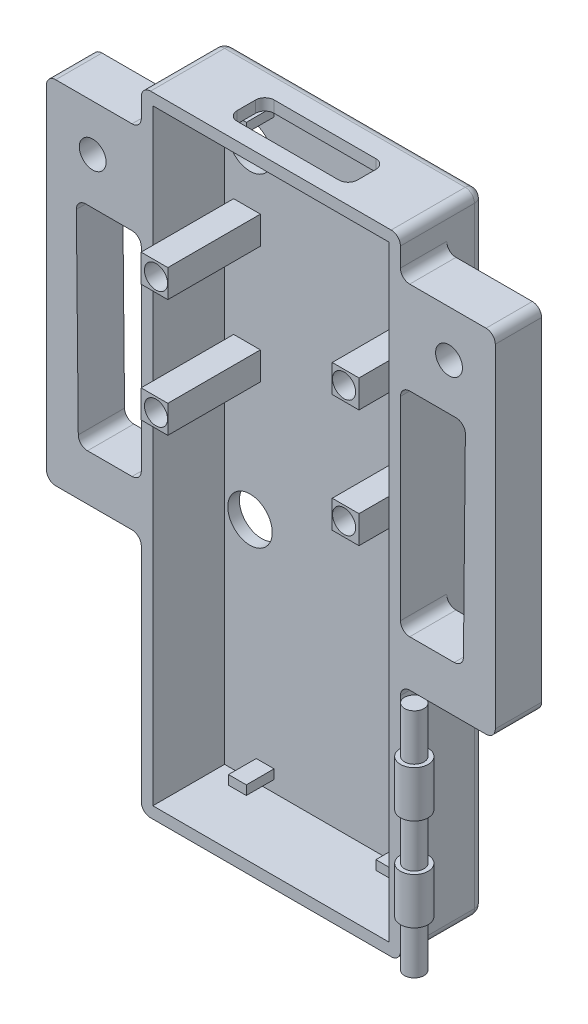
SolidWorks part; units mm, degrees
ref_plane "Front Plane" through (0, 0, 0) normal (0, 0, 1) x (1, 0, 0)
ref_plane "Top Plane" through (0, 0, 0) normal (0, 1, 0) x (1, 0, 0)
ref_plane "Right Plane" through (0, 0, 0) normal (1, 0, 0) x (0, 0, -1)
sketch "Sketch1" plane through (0, 0, 0) normal (0, 0, 1) x (1, 0, 0)
  line L0 (-14, 34) -> (14, -34) construction
  line L1 (-14, 34) -> (14, 34)
  line L2 (-14, 34) -> (-14, -34)
  line L3 (-14, -34) -> (14, -34)
  line L4 (14, 34) -> (14, -34)
  point P4 (0, 0)
  dimension "D1" = 68
  dimension "D2" = 28
extrude "Boss-Extrude1" add sketch "Sketch1" along normal blind 1.25
sketch "Sketch21" plane through (0, 0, 1.25) normal (0, 0, 1) x (1, 0, 0)
  line L0 (-14, 34) -> (-14, 31.5) construction
  line L1 (-14, 34) -> (-14, -34) construction
  line L2 (-9.3284, 30.5) -> (-9.3284, -30.4933) construction
  line L3 (-14, 0.0033) -> (14, 0.0033) construction
  line L4 (14, -34) -> (14, 34) construction
  line L5 (-0.4034, 30.5) -> (6.5966, 30.5) construction
  line L6 (-0.4034, 30.5) -> (-7.4034, 30.5) construction
  line L7 (-7.4034, 30.5) -> (-9.3284, 30.5)
  line L8 (-7.4034, 30.5) -> (-7.4034, 31.5)
  line L9 (-7.4034, 31.5) -> (-9.3284, 31.5)
  line L10 (-9.3284, 30.5) -> (-9.3284, 31.5)
  line L11 (6.5966, 30.5) -> (8.5216, 30.5)
  line L12 (6.5966, 30.5) -> (6.5966, 31.5)
  line L13 (6.5966, 31.5) -> (8.5216, 31.5)
  line L14 (8.5216, 30.5) -> (8.5216, 31.5)
  line L15 (6.5966, -31.4933) -> (8.5216, -31.4933)
  line L16 (8.5216, -30.4933) -> (8.5216, -31.4933)
  line L17 (6.5966, -30.4933) -> (8.5216, -30.4933)
  line L18 (6.5966, -30.4933) -> (6.5966, -31.4933)
  line L19 (-7.4034, -31.4933) -> (-9.3284, -31.4933)
  line L20 (-9.3284, -30.4933) -> (-9.3284, -31.4933)
  line L21 (-7.4034, -30.4933) -> (-9.3284, -30.4933)
  line L22 (-7.4034, -30.4933) -> (-7.4034, -31.4933)
  line L23 (-14, -34) -> (14, -34) construction
  line L24 (8.5216, 30.5) -> (8.5216, -30.4933) construction
  line L25 (7.5591, 31.5) -> (7.5591, 34) construction
  line L26 (14, 34) -> (-14, 34) construction
  line L27 (-7.4034, -31.4933) -> (6.5966, -31.4933) construction
  line L28 (-7.4034, 30.5) -> (-7.4034, 0.0033) construction
  dimension "D1" = 1.925
  dimension "D2" = 1
  dimension "D3" = 1.925
  dimension "D4" = 1
  dimension "D5" = 60.9933
  dimension "D6" = 60.9933
extrude "Boss-Extrude10" add sketch "Sketch21" along normal blind 3
sketch "Sketch22" plane through (0, 0, 1.25) normal (0, 0, 1) x (1, 0, 0)
  line L0 (-11.7716, 7.9708) -> (-14, 7.9708) construction
  line L1 (0, 34) -> (0, 0) construction
  line L2 (8.8816, 20.6708) -> (11.7716, 20.6708)
  line L3 (8.8816, 20.6708) -> (8.8816, 17.6708)
  line L4 (8.8816, 17.6708) -> (11.7716, 17.6708)
  line L5 (11.7716, 20.6708) -> (11.7716, 17.6708)
  line L6 (14, 34) -> (-14, 34) construction
  line L7 (-10.16, 6.4708) -> (10.16, 6.4708) construction
  line L8 (-8.8816, 17.6708) -> (-11.7716, 17.6708)
  line L9 (-11.7716, 20.6708) -> (-11.7716, 17.6708)
  line L10 (-8.8816, 20.6708) -> (-11.7716, 20.6708)
  line L11 (-8.8816, 20.6708) -> (-8.8816, 17.6708)
  line L12 (11.7716, 7.9708) -> (14, 7.9708) construction
  line L15 (11.7716, 4.9708) -> (14, 4.9708) construction
  line L16 (8.8816, 7.9708) -> (11.7716, 7.9708)
  line L17 (11.7716, 4.9708) -> (11.7716, 7.9708)
  line L18 (8.8816, 4.9708) -> (11.7716, 4.9708)
  line L19 (8.8816, 4.9708) -> (8.8816, 7.9708)
  line L20 (-8.8816, 4.9708) -> (-8.8816, 7.9708)
  line L21 (-8.8816, 4.9708) -> (-11.7716, 4.9708)
  line L22 (-11.7716, 4.9708) -> (-11.7716, 7.9708)
  line L23 (-8.8816, 7.9708) -> (-11.7716, 7.9708)
  line L24 (14, -34) -> (14, 34) construction
  line L25 (-11.7716, 4.9708) -> (-14, 4.9708) construction
  line L26 (-14, 34) -> (-14, -34) construction
  circle A0 centre (10.16, 19.1708) radius 1.25
  circle A1 centre (-10.16, 19.1708) radius 1.25
  circle A2 centre (10.16, 6.4708) radius 1.25
  circle A3 centre (-10.16, 6.4708) radius 1.25
  dimension "D3" = 2.5
  dimension "D1" = 3
  dimension "D2" = 2.89
  dimension "D7" = 3
extrude "Boss-Extrude11" add sketch "Sketch22" along normal blind 10
sketch "Sketch7" plane through (0, 0, 1.25) normal (0, 0, 1) x (1, 0, 0)
  line L0 (14, -34) -> (14, 34) construction
  line L1 (-12.75, 32.75) -> (12.75, 32.75)
  line L2 (-12.75, 32.75) -> (-12.75, -32.75)
  line L3 (-12.75, -32.75) -> (12.75, -32.75)
  line L4 (12.75, 32.75) -> (12.75, -32.75)
  line L5 (14, 34) -> (-14, 34) construction
  line L6 (-14, 34) -> (-14, -34) construction
  line L7 (-14, -34) -> (14, -34) construction
  line L9 (-14, 34) -> (14, 34)
  line L10 (-14, 34) -> (-14, -34)
  line L11 (-14, -34) -> (14, -34)
  line L12 (14, 34) -> (14, -34)
  dimension "D1" = 1.25
  dimension "D2" = 1.25
  dimension "D3" = 1.25
  dimension "D4" = 1.25
extrude "Boss-Extrude4" add sketch "Sketch7" along normal blind 7.75
sketch "Sketch18" plane through (0, 34, 0) normal (0, 1, 0) x (1, 0, 0)
  line L0 (0, 0) -> (0, -5.15) construction
  line L1 (14, 0) -> (-14, 0) construction
  line L3 (-6.5, -3.15) -> (6.5, -3.15)
  line L4 (-6.5, -3.15) -> (-6.5, -7.15)
  line L5 (-6.5, -7.15) -> (6.5, -7.15)
  line L6 (6.5, -3.15) -> (6.5, -7.15)
  line L7 (-6.5, -3.15) -> (6.5, -7.15) construction
  line L8 (-6.5, -7.15) -> (6.5, -3.15) construction
  dimension "D1" = 13
  dimension "D2" = 4
  dimension "D3" = 3.15
extrude "Cut-Extrude10" cut sketch "Sketch18" against normal up to surface (1.25 mm away) up to face at (0, 32.75, 5.125)
sketch "Sketch17" plane through (0, 0, 1.25) normal (0, 0, 1) x (1, 0, 0)
  line L0 (14, 34) -> (-14, 34) construction
  line L1 (5.5, 35.25) -> (-5.5, 35.25)
  line L2 (5.5, 35.25) -> (5.5, 32.75)
  line L3 (5.5, 32.75) -> (-5.5, 32.75)
  line L4 (-5.5, 35.25) -> (-5.5, 32.75)
  line L5 (5.5, 35.25) -> (-5.5, 32.75) construction
  line L6 (5.5, 32.75) -> (-5.5, 35.25) construction
  line L7 (12.75, 32.75) -> (-12.75, 32.75) construction
  point P0 (0, 34)
  dimension "D1" = 11
sketch "Sketch13" plane through (0, -34, 0) normal (0, -1, 0) x (1, 0, 0)
  line L0 (14, 9) -> (15.5, 9) construction
  line L1 (15.5, 7.5) -> (14, 6.3032)
  line L2 (14, 9) -> (14, 0) construction
  line L3 (14, 9) -> (14, 6.3032)
  line L4 (-14, 0) -> (14, 0) construction
  arc A0 (15.5, 7.5) -> (14, 9) centre (15.5, 9) ccw
  circle A1 centre (15.5, 9) radius 1.05
  dimension "D1" = 2.1
  dimension "D2" = 1.5
  dimension "D3" = 6.3032
extrude "Boss-Extrude7" add sketch "Sketch13" against normal blind 5
pattern_linear "LPattern2" count 4 spacing 5 along (0, 1, 0) skipping (2, 0) of "Boss-Extrude7"
sketch "Sketch14" plane through (14, 0, 0) normal (1, 0, 0) x (0, 0, -1)
  line L1 (-11.8523, -34) -> (-1.8523, -34)
  line L2 (-11.8523, -34) -> (-11.8523, -29)
  line L3 (-11.8523, -29) -> (-1.8523, -29)
  line L4 (-1.8523, -34) -> (-1.8523, -29)
  line L6 (-6.3032, -34) -> (0, -34) construction
  dimension "D1" = 5
  dimension "D2" = 10
extrude "Cut-Extrude5" cut sketch "Sketch14" along normal blind 5
sketch "Sketch5" [suppressed] plane through (0, 0, 1.25) normal (0, 0, 1) x (1, 0, 0)
  line L0 (-2.3257, 30.0894) -> (-2.3257, -35.4106) construction
  line L1 (9.9243, 30.0894) -> (-14.5757, 30.0894) construction
  line L2 (-14.5757, -35.4106) -> (9.9243, -35.4106) construction
  line L3 (-14.5757, -2.6606) -> (9.9243, -2.6606) construction
  line L4 (-14.5757, 30.0894) -> (-14.5757, -35.4106) construction
  line L5 (9.9243, -35.4106) -> (9.9243, 30.0894) construction
  circle A4 centre (-2.3257, 21.3394) radius 2.1
  circle A10 centre (-2.3257, 13.3394) radius 2.1
  circle A11 centre (-2.3257, 5.3394) radius 2.1
  circle A12 centre (-2.3257, -2.6606) radius 2.1
  circle A13 centre (-2.3257, -10.6606) radius 2.1
  circle A14 centre (-2.3257, -18.6606) radius 2.1
  circle A15 centre (-2.3257, -26.6606) radius 2.1
  dimension "D1" = 4.2
  dimension "D2" = 7
extrude "Cut-Extrude3" [suppressed] cut sketch "Sketch5" against normal through all
fillet "Fillet1" radius 1 8 edges at (0, 34, 0) (14, 0, 0) (-14, 0, 0) (0, -34, 0) (14, 34, 4.5) (14, -34, 4.5) (-14, -34, 4.5) (-14, 34, 4.5)
sketch "Sketch8" plane through (0, 0, 1.25) normal (0, 0, 1) x (1, 0, 0)
  line L0 (-10.75, 32.75) -> (-12.75, 30.75)
  line L1 (12.75, 32.75) -> (-12.75, 32.75) construction
  line L2 (-12.75, 32.75) -> (-12.75, -32.75) construction
  line L3 (-10.75, 32.75) -> (-12.75, 32.75)
  line L4 (-12.75, 32.75) -> (-12.75, 30.75)
  line L5 (-12.75, -32.5698) -> (-12.75, -34.744)
  line L6 (-12.75, 32.75) -> (-12.75, -32.75) construction
  line L7 (-12.75, -34.744) -> (-12.9043, -32.75)
  line L8 (-12.75, -32.75) -> (12.75, -32.75) construction
  line L9 (-12.9043, -32.75) -> (-12.75, -32.5698)
  line L10 (0, 32.75) -> (0, 24.115) construction
  line L11 (12.75, 32.75) -> (-12.75, 32.75) construction
  line L12 (12.9043, -32.75) -> (12.75, -32.5698)
  line L13 (12.75, -34.744) -> (12.9043, -32.75)
  line L14 (12.75, -32.5698) -> (12.75, -34.744)
  line L15 (12.75, 32.75) -> (12.75, 30.75)
  line L16 (10.75, 32.75) -> (12.75, 32.75)
  line L17 (10.75, 32.75) -> (12.75, 30.75)
  dimension "D1" = 2
  dimension "D2" = 45
  dimension "D3" = 2
  dimension "D4" = 45
extrude "Boss-Extrude5" [suppressed] add sketch "Sketch8" along normal blind 5.75
fillet "Fillet7" radius 1 4 edges at (-6.5, 33.375, 3.15) (-6.5, 33.375, 7.15) (6.5, 33.375, 3.15) (6.5, 33.375, 7.15)
sketch "Sketch23" plane through (0, 0, 1.25) normal (0, 0, 1) x (1, 0, 0)
  line L0 (-10, 26.5252) -> (-10, -8.4748)
  line L3 (10, 26.5252) -> (-10, 26.5252)
  line L4 (0, 26.5252) -> (10, 26.5252)
  line L5 (-10, -8.4748) -> (10, -8.4748)
  line L6 (10, -8.4748) -> (10, 26.5252)
hole_wizard "M4 Clearance Hole1" positions "Sketch24" profile "Sketch25" hole size "M4" standard "ANSI Metric" end condition through all
sketch "Sketch24" plane through (0, 0, 1.25) normal (0, 0, 1) x (1, 0, 0)
  point P0 (-10, 26.5252)
  point P3 (10, 26.5252)
  point P6 (10, -8.4748)
  point P9 (-10, -8.4748)
sketch "Sketch25" plane through (-10, 26.5252, 1.25) normal (1, 0, 0) x (0, -1, 0)
  line L0 (0, 0) -> (0, 1.25)
  line L1 (0, 1.25) -> (2.4, 1.25)
  line L2 (2.4, 1.25) -> (2.4, 0)
  line L5 (2.4, 0) -> (0, 0)
  line L11 (0, -6.35) -> (0, 107.95) construction
  dimension "Thru Hole Dia." = 4.8
  dimension "Thru Hole Depth" = 1.25
sketch "Sketch26" plane through (0, 0, 9) normal (0, 0, 1) x (1, 0, 0)
  line L0 (-14, 33) -> (-14, -33) construction
  line L1 (-14, 29.9398) -> (-24.25, 29.9398)
  line L2 (-24.25, 29.9398) -> (-24.25, -8.0602)
  line L3 (-24.25, -8.0602) -> (-14, -8.0602)
  line L4 (-19.25, 24.9414) -> (-14, 24.9414) construction
  line L5 (-19.25, 24.9414) -> (-24.25, 24.9414) construction
  line L6 (-20.7, 24.9414) -> (-20.7, 29.9398) construction
  line L7 (-17.8, 24.9414) -> (-17.8, 19.9398) construction
  line L8 (-21.025, 19.9398) -> (-14, 19.9398)
  line L9 (-20.8, -3.0602) -> (-14, -3.0602)
  line L10 (-14, 29.9398) -> (-14, 19.9398)
  line L11 (-20.8, -3.0602) -> (-21.025, 19.9398)
  line L12 (-14, -3.0602) -> (-14, -8.0602)
  line L13 (-19.25, 24.9414) -> (-19.125, 29.9398) construction
  circle A0 centre (-19.25, 24.9414) radius 1.45
  dimension "D1" = 2.9
  dimension "D2" = 38
  dimension "D3" = 5.25
  dimension "D5" = 23
  dimension "D7" = 7.025
extrude "Boss-Extrude12" add sketch "Sketch26" against normal blind 5
fillet "Fillet10" radius 1 8 edges at (-14, 19.9398, 6.5) (-14, -3.0602, 6.5) (-20.8, -3.0602, 6.5) (-21.025, 19.9398, 6.5) (-14, 29.9398, 6.5) (-14, -8.0602, 6.5) (-24.25, -8.0602, 6.5) (-24.25, 29.9398, 6.5)
sketch "Sketch27" plane through (0, 0, 1.25) normal (0, 0, 1) x (1, 0, 0)
  line L0 (0, 32.7214) -> (0, -32.75) construction
  line L1 (-12.75, -32.75) -> (12.75, -32.75) construction
  line L2 (12.75, -32.75) -> (12.75, 32.75) construction
  line L3 (12.75, 0) -> (-12.75, 0) construction
  line L4 (-12.75, 32.75) -> (-12.75, -32.75) construction
ref_axis "Axis1" through (0, 32.7214, 1.25) along (0, -1, 0)
ref_plane "Plane1" through (0, 0, 0) normal (-1, 0, 0) x (0, 0, 1)
mirror "Mirror2" about plane through (0, 0, 0) normal (-1, 0, 0) of "Boss-Extrude12"
fillet "Fillet12" radius 1 8 edges at (21.025, 19.9398, 6.5) (14, 19.9398, 6.5) (20.8, -3.0602, 6.5) (14, -3.0602, 6.5) (14, -8.0602, 6.5) (24.25, -8.0602, 6.5) (24.25, 29.9398, 6.5) (14, 29.9398, 6.5)
sketch "Sketch28" plane through (0, -29, 0) normal (0, -1, 0) x (-1, 0, 0)
  line L0 (-15.5, -10.05) -> (-15.5, -7.95) construction
  circle A1 centre (-15.5, -9) radius 1.05 construction
  circle A2 centre (-15.5, -9) radius 1.05
  dimension "D1" = 2.1
extrude "Boss-Extrude13" add sketch "Sketch28" along normal blind 5 and the other way blind 20
sketch "Sketch29" plane through (0, 0, 11.25) normal (0, 0, 1) x (1, 0, 0)
  circle A0 centre (-10.16, 19.1708) radius 1.25
  circle A1 centre (-10.16, 6.4708) radius 1.25
  circle A2 centre (10.16, 6.4708) radius 1.25
  circle A3 centre (10.16, 19.1708) radius 1.25
extrude "Cut-Extrude11" cut sketch "Sketch29" against normal through all and the other way through all
